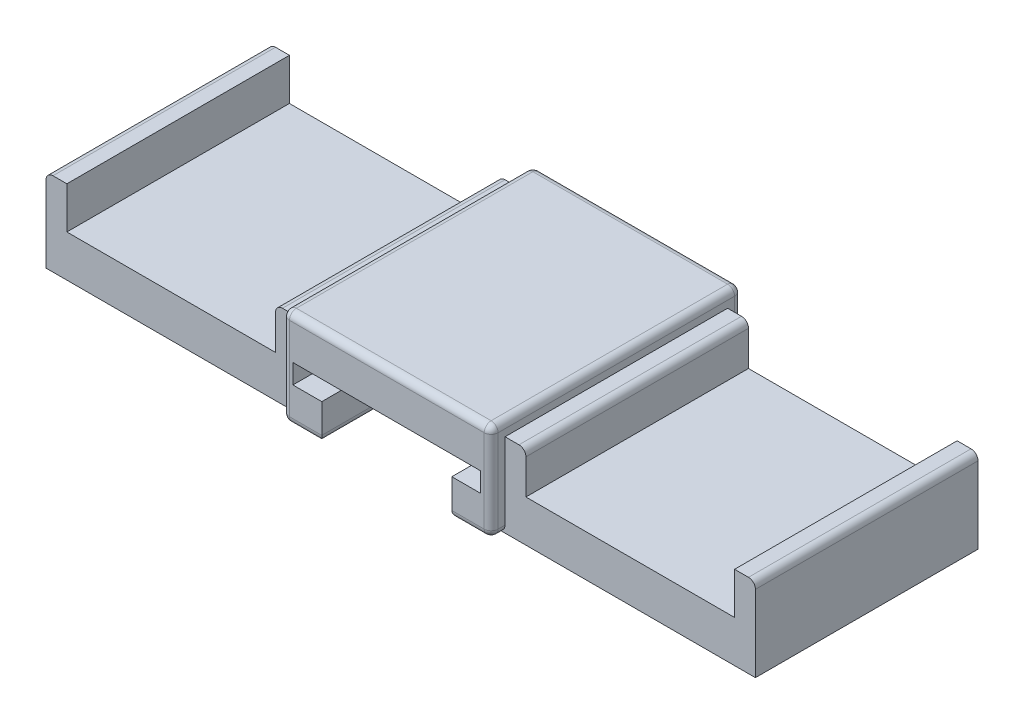
SolidWorks part; units mm, degrees
ref_plane "Front Plane" through (0, 0, 0) normal (0, 0, 1) x (1, 0, 0)
ref_plane "Top Plane" through (0, 0, 0) normal (0, 1, 0) x (1, 0, 0)
ref_plane "Right Plane" through (0, 0, 0) normal (1, 0, 0) x (0, 0, -1)
sketch "Sketch1" plane through (0, 0, 0) normal (0, 1, 0) x (1, 0, 0)
  line L1 (-7.5, -9) -> (7.5, -9)
  line L2 (-7.5, -9) -> (-7.5, 9)
  line L3 (-7.5, 9) -> (7.5, 9)
  line L4 (7.5, -9) -> (7.5, 9)
  line L5 (-7.5, -9) -> (7.5, 9) construction
  line L6 (-7.5, 9) -> (7.5, -9) construction
  point P0 (0, 0)
  dimension "D1" = 18
  dimension "D2" = 15
extrude "Boss-Extrude1" add sketch "Sketch1" along normal blind 7
sketch "Sketch2" plane through (0, 0, 9) normal (0, 0, 1) x (1, 0, 0)
  line L0 (-6.75, 0) -> (6.75, 0)
  line L1 (-7.5, 0) -> (7.5, 0) construction
  line L2 (6.75, 0) -> (6.75, 4)
  line L3 (6.75, 4) -> (-6.75, 4)
  line L4 (-6.75, 4) -> (-6.75, 0)
  line L5 (-6.75, 2.6) -> (6.75, 2.6)
  line L6 (-4.675, 2.6) -> (-4.675, 0)
  line L7 (0, 0) -> (0, 7) construction
  line L8 (-7.5, 7) -> (7.5, 7) construction
  line L9 (4.675, 2.6) -> (4.675, 0)
  line L10 (-0.6, 0) -> (-0.6, 5)
  line L11 (-0.6, 5) -> (0.6, 5)
  line L12 (0.6, 5) -> (0.6, 0)
  line L13 (1.1, 2.6) -> (1.1, 0)
  line L14 (-1.1, 2.6) -> (-1.1, 0)
  point P6 (0, 0)
  dimension "D1" = 4
  dimension "D2" = 1.4
  dimension "D3" = 9.35
  dimension "D4" = 1.2
  dimension "0.5" = 0.5
  dimension "D6" = 13.5
extrude "Cut-Extrude1" cut sketch "Sketch2" against normal blind 14.2 contours L5 L10 L3 L4 | L3 L12 L5 L2 | L14 L5 L6 L0 | L5 L13 L4 L9 | L7 L0 L12 L5 | L4 L7 L5 L10 | L5 L7 L3 L10 | L7 L5 L12 L3 region at (-2.8875, 1.3, 9) region at (-3.675, 3.3, 9) region at (-0.3, 1.3, 9) region at (-0.3, 3.3, 9) region at (0.3, 1.3, 9) region at (0.3, 3.3, 9) region at (3.675, 3.3, 9) region at (2.8875, 1.3, 9)
sketch "Sketch8" plane through (0, 0, 9) normal (0, 0, 1) x (1, 0, 0)
  line L0 (-1.1, 2.6) -> (-0.6, 2.6)
  line L1 (-0.6, 2.6) -> (-0.6, 0)
  line L2 (-0.6, 0) -> (-1.1, 0)
  line L3 (-1.1, 0) -> (-1.1, 2.6)
  line L4 (0.6, 2.6) -> (1.1, 2.6)
  line L5 (1.1, 2.6) -> (1.1, 0)
  line L6 (1.1, 0) -> (0.6, 0)
  line L7 (0.6, 0) -> (0.6, 2.6)
extrude "Cut-Extrude4" cut sketch "Sketch8" against normal blind 10
sketch "Sketch9" plane through (-7.5, 0, 0) normal (-1, 0, 0) x (0, 0, 1)
  line L0 (-8, 0) -> (-8, 6)
  line L1 (9, 0) -> (-9, 0) construction
  line L2 (-8, 6) -> (8, 6)
  line L3 (8, 6) -> (8, 0)
  line L4 (-9, 0) -> (9, 0) construction
  line L5 (8, 0) -> (-8, 0)
  line L6 (-0.3093, 0) -> (0, 0) construction
  line L7 (0, 0) -> (0, 6) construction
  dimension "D1" = 16
  dimension "D2" = 6
extrude "Boss-Extrude2" add sketch "Sketch9" along normal blind 18
sketch "Sketch12" plane through (0, 0, 8) normal (0, 0, 1) x (1, 0, 0)
  line L0 (-16.5, 0) -> (-16.5, 6) construction
  line L1 (-25.5, 0) -> (-7.5, 0) construction
  line L2 (-25.5, 6) -> (-7.5, 6) construction
  dimension "D1" = 16.5
sketch "Sketch13" plane through (7.5, 0, 0) normal (1, 0, 0) x (0, 0, -1)
  line L0 (-8, 0) -> (-8, 6)
  line L1 (-8, 0) -> (-8, 6) construction
  line L2 (-8, 6) -> (8, 6)
  line L3 (8, 6) -> (8, 0)
  line L4 (9, 0) -> (-9, 0) construction
  line L5 (8, 0) -> (-8, 0)
  line L6 (0, 0) -> (0, 7) construction
  line L7 (-9, 0) -> (9, 0) construction
  line L8 (-9, 7) -> (9, 7) construction
  dimension "D2" = 6
extrude "Boss-Extrude3" add sketch "Sketch13" along normal blind 18
sketch "Sketch14" plane through (0, 0, 9) normal (0, 0, 1) x (1, 0, 0)
  line L0 (0, 0) -> (0, 7) construction
  line L1 (-7.5, 7) -> (7.5, 7) construction
  line L3 (25.5, 0) -> (7.5, 0) construction
  line L7 (16.5, 0) -> (16.5, 0.2814) construction
  line L12 (16.5, 0) -> (16.5, 6) construction
  line L13 (25.5, 6) -> (7.5, 6) construction
  line L17 (9, 6) -> (9, 3)
  line L18 (9, 3) -> (24, 3)
  line L19 (24, 3) -> (24, 6)
  line L20 (24, 6) -> (9, 6)
  line L23 (-24, 3) -> (-24, 6)
  line L24 (-9, 3) -> (-24, 3)
  line L25 (-9, 6) -> (-9, 3)
  line L30 (-24, 6) -> (-9, 6)
  dimension "D1" = 15
  dimension "D2" = 3
extrude "Cut-Extrude5" cut sketch "Sketch14" against normal blind 32.55
fillet "Fillet1" radius 0.5 21 edges at (0, 0, -9) (7.5, 0, -8.5) (-7.5, 0, -8.5) (-7.5, 0, 8.5) (7.5, 0, 8.5) (7.5, 7, 0) (25.5, 6, 0) (-25.5, 6, 0) (-7.5, 7, 0) (-7.5, 3.5, 9) (7.5, 3.5, 9) (6.0875, 0, 9) (4.675, 0, 1.9) (-4.675, 0, 1.9) (-6.0875, 0, 9) (0, 7, 9) (0, 7, -9) (7.5, 3.5, -9) (-7.5, 3.5, -9) (-9, 6, 0) (9, 6, 0)
